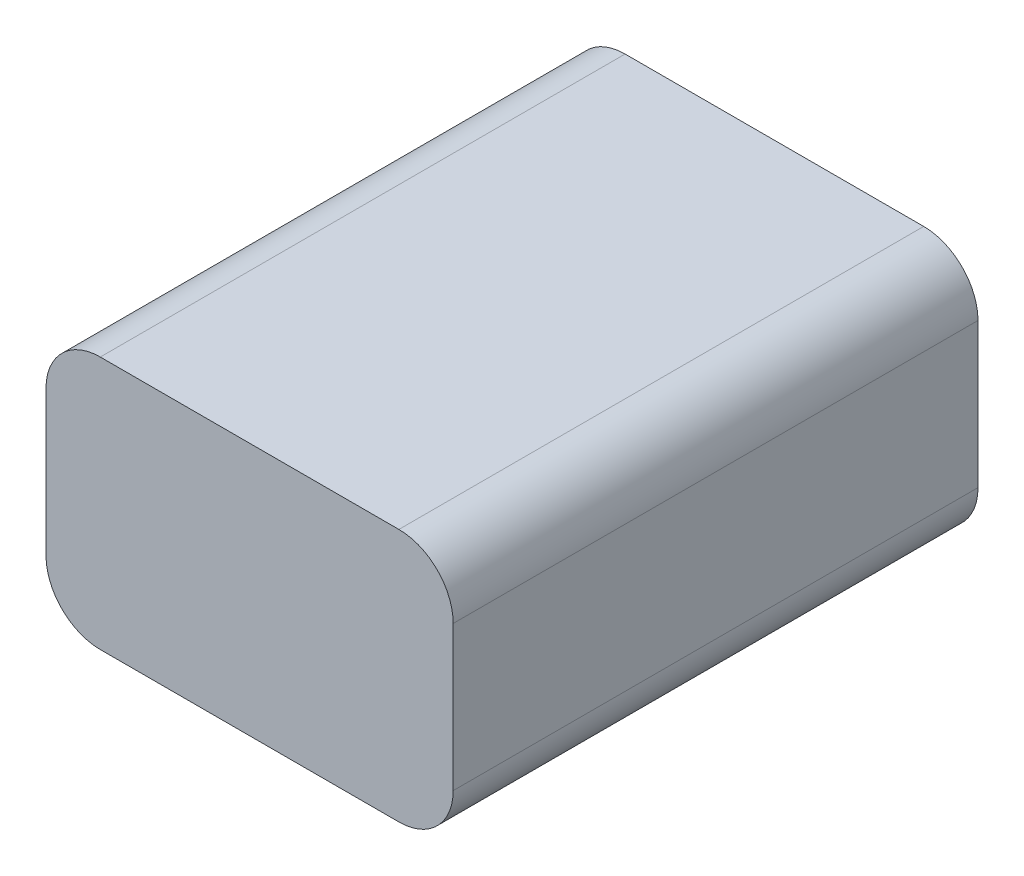
SolidWorks part; units mm, degrees
ref_plane "Front Plane" through (0, 0, 0) normal (0, 0, 1) x (1, 0, 0)
ref_plane "Top Plane" through (0, 0, 0) normal (0, 1, 0) x (1, 0, 0)
ref_plane "Right Plane" through (0, 0, 0) normal (1, 0, 0) x (0, 0, -1)
sketch "Sketch1" plane through (0, 0, 0) normal (0, 0, 1) x (1, 0, 0)
  line L1 (-22.5, 14) -> (22.5, 14)
  line L2 (-22.5, 14) -> (-22.5, -14)
  line L3 (-22.5, -14) -> (22.5, -14)
  line L4 (22.5, 14) -> (22.5, -14)
  line L5 (-22.5, 14) -> (22.5, -14) construction
  line L6 (-22.5, -14) -> (22.5, 14) construction
  point P0 (0, 0)
  dimension "D1" = 45
  dimension "D2" = 28
extrude "Boss-Extrude1" add sketch "Sketch1" along normal blind 29 and the other way blind 29
fillet "Fillet1" radius 6 4 edges at (-22.5, -14, 0) (22.5, -14, 0) (22.5, 14, 0) (-22.5, 14, 0)
